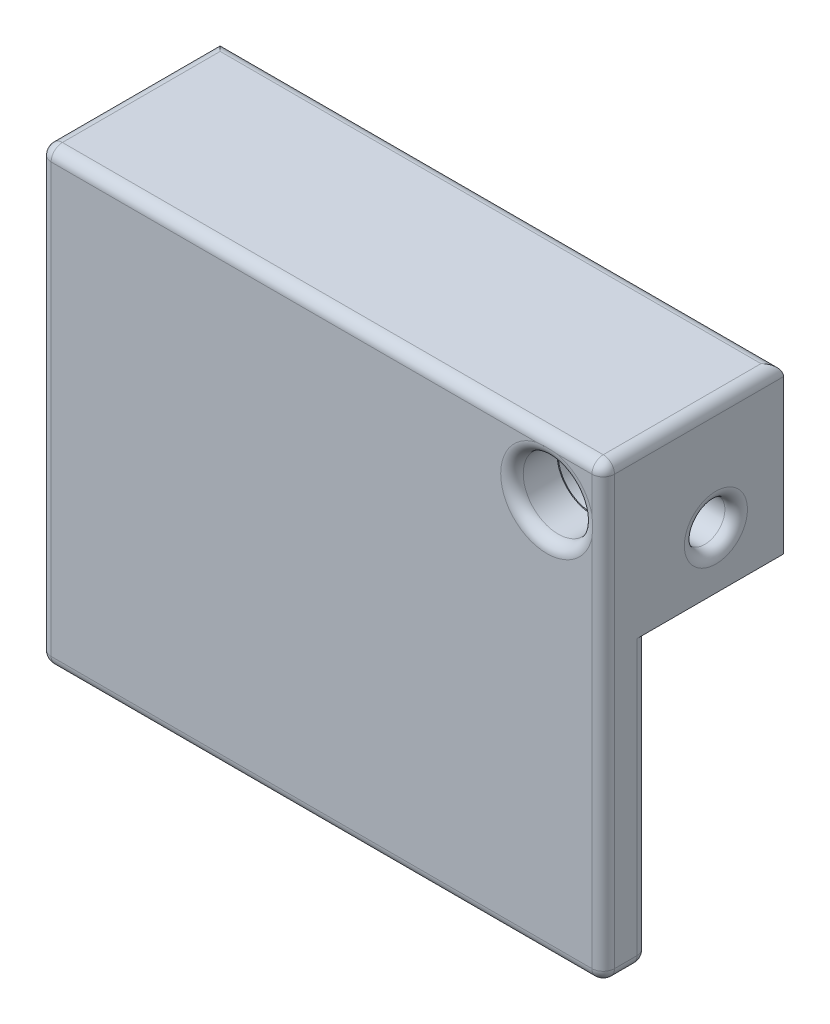
SolidWorks part; units mm, degrees
ref_plane "Plan de face" through (0, 0, 0) normal (0, 0, 1) x (1, 0, 0)
ref_plane "Plan de dessus" through (0, 0, 0) normal (0, 1, 0) x (1, 0, 0)
ref_plane "Plan de droite" through (0, 0, 0) normal (1, 0, 0) x (0, 0, -1)
sketch "Esquisse1" plane through (0, 0, 0) normal (0, 0, 1) x (1, 0, 0)
  line L1 (0, 0) -> (25, 0)
  line L2 (0, 0) -> (0, 20)
  line L3 (0, 20) -> (25, 20)
  line L4 (25, 0) -> (25, 20)
  circle A0 centre (22.5, 17.5) radius 1.55
  dimension "D3" = 2.5
  dimension "D5" = 3.1
  dimension "D1" = 20
  dimension "D2" = 25
  dimension "D4" = 2.5
extrude "Boss.-Extru.1" add sketch "Esquisse1" along normal blind 2
sketch "Esquisse2" plane through (0, 0, 0) normal (0, 0, -1) x (-1, 0, 0)
  line L0 (0, 20) -> (0, 0) construction
  line L1 (-18.6889, 12.684) -> (-18.6889, 15.3557)
  line L2 (-1.8, 13.2884) -> (-4.4421, 13.2884)
  line L3 (0, 13.5655) -> (0, 20)
  line L4 (0, 20) -> (-25, 20)
  line L5 (-25, 12.684) -> (-25, 20)
  line L6 (-18.6889, 15.3557) -> (-18.1917, 15.8529)
  line L7 (-18.1917, 15.8529) -> (-6.7056, 15.8529)
  line L8 (-6.7056, 15.8529) -> (-4.4421, 13.5894)
  line L9 (-4.4421, 13.5894) -> (-4.4421, 13.2884)
  line L10 (-18.6889, 12.684) -> (-25, 12.684)
  line L13 (0, 13.5655) -> (0, 2)
  line L15 (-1.8, 13.2884) -> (-1.8, 2)
  line L16 (-1.8, 2) -> (0, 2)
  line L17 (0, 0) -> (-25, 0) construction
  circle A1 centre (-22.5, 17.5) radius 1.5
  point P11 (0, 0)
  point P17 (-6.4393, 15.5866)
  point P18 (-19.2215, 15.2138)
  point P19 (-18.1297, 15.8529)
  point P20 (-18.6889, 15.3557)
  dimension "D2" = 2
  dimension "D1" = 1.8
extrude "Boss.-Extru.2" add sketch "Esquisse2" along normal blind 6
sketch "Esquisse3" plane through (1.8, 0, 0) normal (1, 0, 0) x (0, 0, -1)
  line L0 (6, 13.2884) -> (6, 2) construction
  line L2 (-2, 0) -> (0, 0) construction
  circle A0 centre (3, 8) radius 2
  dimension "D1" = 4
  dimension "D2" = 3
  dimension "D3" = 8
extrude "Enlèv. mat.-Extru.1" cut sketch "Esquisse3" against normal blind 1
sketch "Esquisse4" plane through (0, 0, 0) normal (-1, 0, 0) x (0, 0, 1)
  line L0 (-6, 2) -> (-6, 20) construction
  line L1 (2, 20) -> (-6, 20) construction
  circle A0 centre (-3, 15.2) radius 0.9
  dimension "D1" = 3
  dimension "D2" = 1.8
  dimension "D3" = 4.8
extrude "Enlèv. mat.-Extru.2" cut sketch "Esquisse4" against normal through all
fillet "Congé1" radius 0.5 3 edges at (18.6889, 14.3, -3) (0, 15.2, -2.1) (25, 15.2, -2.1)
fillet "Congé5" radius 0.5 11 edges at (0, 0, 1) (25, 0, 1) (12.5, 0, 0) (0, 20, -2) (12.5, 20, -6) (25, 20, -2) (24.05, 17.5, 2) (12.5, 20, 2) (25, 10, 2) (12.5, 0, 2) (0, 10, 2)
fillet "Congé6" radius 0.5 2 edges at (24.8536, 0.1464, 0.1464) (25, 6.592, 0)
